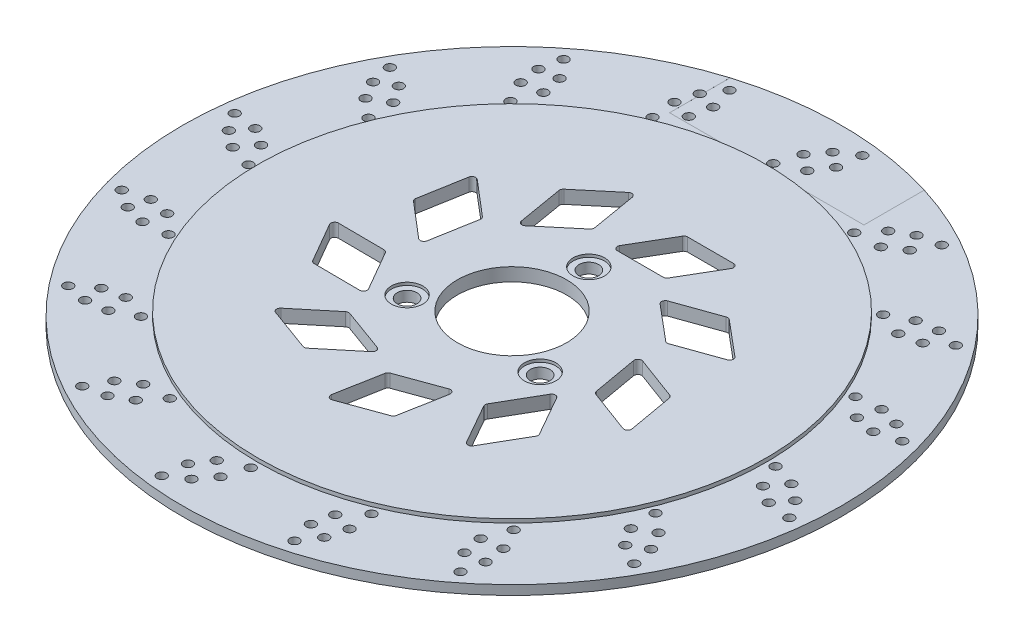
SolidWorks part; units mm, degrees
ref_plane "Płaszczyzna przednia" through (0, 0, 0) normal (0, 0, 1) x (1, 0, 0)
ref_plane "Płaszczyzna górna" through (0, 0, 0) normal (0, 1, 0) x (1, 0, 0)
ref_plane "Płaszczyzna prawa" through (0, 0, 0) normal (1, 0, 0) x (0, 0, -1)
sketch "Sketch1" plane through (0, 0, 0) normal (0, 1, 0) x (1, 0, 0)
  circle A0 centre (0, 0) radius 29
  circle A1 centre (0, 0) radius 175
  circle A2 centre (0, 0) radius 135
  dimension "D1" = 58
  dimension "D2" = 350
  dimension "D3" = 270
extrude "Boss-Extrude1" add sketch "Sketch1" along normal blind 7 contours A2 A0 region at (-131.1816, 0, 0)
extrude "Boss-Extrude2" add sketch "Sketch1<3>" along normal blind 5 contours A1 A2 region at (-170.0503, 0, 0)
sketch "Sketch1<3>" plane through (0, 0, 0) normal (0, 1, 0) x (1, 0, 0) same geometry as "Sketch1"
ref_plane "mocowanie tarczy" through (0, 7, 0) normal (0, 1, 0) x (1, 0, 0)
sketch "Sketch7" plane through (0, 7, 0) normal (0, 1, 0) x (1, 0, 0)
  circle A0 centre (0, 0) radius 40.8 construction
  circle A2 centre (0, 40.8) radius 5.2
  dimension "D1" = 81.6
  dimension "D3" = 10.4
extrude "Cut-Extrude9" cut sketch "Sketch7" against normal through all contours A2 region at (0, 7, -40.8)
sketch "Sketch11" plane through (0, 7, 0) normal (0, 1, 0) x (1, 0, 0)
  circle A0 centre (0, 40.8) radius 8.35
  dimension "D1" = 16.7
extrude "Cut-Extrude10" cut sketch "Sketch11" against normal blind 1.5 contours A0 region at (0, 7, -40.8)
pattern_circular "CirPattern1" count 3 over 360 about axis through (0, 7, 0) along (0, 1, 0) of "Cut-Extrude9"
pattern_circular "CirPattern2" count 3 over 360 about axis through (0, 7, 0) along (0, 1, 0) of "Cut-Extrude10"
ref_plane "dziury przy mocowaniu" through (0, 7, 0) normal (0, 1, 0) x (1, 0, 0)
sketch "Sketch13" plane through (0, 7, 0) normal (0, 1, 0) x (1, 0, 0)
  line L0 (0.1257, 55.8) -> (24.4722, 55.8)
  line L1 (26.1973, 56.788) -> (38.5161, 77.788)
  line L2 (36.791, 80.8) -> (12.4445, 80.8)
  line L3 (10.7194, 79.812) -> (-1.5993, 58.812)
  line L4 (80.1197, 38.2479) -> (61.4692, 53.8976)
  line L5 (59.5126, 54.2495) -> (36.5774, 46.0809)
  line L6 (56.57, 26.6632) -> (79.5052, 34.8318)
  line L7 (35.9629, 42.6648) -> (54.6133, 27.0152)
  line L8 (85.9596, -22.2) -> (81.7318, 1.7766)
  line L9 (80.4592, 3.3039) -> (57.6392, 11.7889)
  line L10 (60.4728, -15.9369) -> (83.2929, -24.4219)
  line L11 (54.9725, 9.567) -> (59.2002, -14.4096)
  line L12 (51.5779, -72.2596) -> (63.7512, -51.1749)
  line L13 (63.7581, -49.1869) -> (51.7309, -28.0186)
  line L14 (36.0798, -51.0793) -> (48.107, -72.2476)
  line L15 (48.2599, -28.0066) -> (36.0867, -49.0913)
  line L16 (-6.9376, -88.5074) -> (15.9406, -80.1804)
  line L17 (17.2237, -78.6619) -> (21.6171, -54.7151)
  line L18 (-5.1954, -62.3203) -> (-9.5888, -86.2671)
  line L19 (18.9659, -52.4748) -> (-3.9123, -60.8018)
  line L20 (-62.207, -63.3409) -> (-39.3288, -71.6678)
  line L21 (-37.3698, -71.3294) -> (-18.6115, -55.8091)
  line L22 (-44.0397, -44.4002) -> (-62.7979, -59.9205)
  line L23 (-19.2025, -52.3888) -> (-42.0807, -44.0618)
  line L24 (-88.3691, -8.5357) -> (-76.1958, -29.6204)
  line L25 (-74.4776, -30.6203) -> (-50.1317, -30.7887)
  line L26 (-62.2773, -5.7041) -> (-86.6232, -5.5357)
  line L27 (-48.3858, -27.7887) -> (-60.5591, -6.704)
  line L28 (-73.1823, 50.2641) -> (-77.41, 26.2875)
  line L29 (-76.7365, 24.4171) -> (-58.1947, 8.6389)
  line L30 (-51.3747, 35.6618) -> (-69.9165, 51.44)
  line L31 (-54.9289, 9.8148) -> (-50.7012, 33.7914)
  line L32 (-23.7527, 85.5456) -> (-42.4032, 69.8959)
  line L33 (-43.0896, 68.0302) -> (-39.0278, 44.0249)
  line L34 (-16.4333, 60.3419) -> (-20.4952, 84.3471)
  line L35 (-35.7702, 42.8265) -> (-17.1197, 58.4761)
  circle A0 centre (0, 40.8) radius 8.35 construction
  arc A1 (38.5161, 77.788) -> (36.791, 80.8) centre (36.791, 78.8) ccw
  arc A2 (24.4722, 55.8) -> (26.1973, 56.788) centre (24.4722, 57.8) ccw
  arc A3 (0.1257, 55.8) -> (-1.5993, 58.812) centre (0.1257, 57.8) cw
  arc A4 (10.7194, 79.812) -> (12.4445, 80.8) centre (12.4445, 78.8) cw
  arc A5 (35.9629, 42.6648) -> (36.5774, 46.0809) centre (37.2484, 44.1969) cw
  arc A6 (59.5126, 54.2495) -> (61.4692, 53.8976) centre (60.1837, 52.3655) cw
  arc A7 (79.5052, 34.8318) -> (80.1197, 38.2479) centre (78.8342, 36.7159) ccw
  arc A8 (54.6133, 27.0152) -> (56.57, 26.6632) centre (55.8989, 28.5473) ccw
  arc A9 (54.9725, 9.567) -> (57.6392, 11.7889) centre (56.9421, 9.9143) cw
  arc A10 (80.4592, 3.3039) -> (81.7318, 1.7766) centre (79.7622, 1.4293) cw
  arc A11 (83.2929, -24.4219) -> (85.9596, -22.2) centre (83.9899, -22.5473) ccw
  arc A12 (59.2002, -14.4096) -> (60.4728, -15.9369) centre (61.1699, -14.0623) ccw
  arc A13 (48.2599, -28.0066) -> (51.7309, -28.0186) centre (49.992, -29.0066) cw
  arc A14 (63.7581, -49.1869) -> (63.7512, -51.1749) centre (62.0191, -50.1749) cw
  arc A15 (48.107, -72.2476) -> (51.5779, -72.2596) centre (49.8459, -71.2596) ccw
  arc A16 (36.0867, -49.0913) -> (36.0798, -51.0793) centre (37.8187, -50.0913) ccw
  arc A17 (18.9659, -52.4748) -> (21.6171, -54.7151) centre (19.65, -54.3542) cw
  arc A18 (17.2237, -78.6619) -> (15.9406, -80.1804) centre (15.2566, -78.301) cw
  arc A19 (-9.5888, -86.2671) -> (-6.9376, -88.5074) centre (-7.6216, -86.628) ccw
  arc A20 (-3.9123, -60.8018) -> (-5.1954, -62.3203) centre (-3.2282, -62.6812) ccw
  arc A21 (-19.2025, -52.3888) -> (-18.6115, -55.8091) centre (-19.8865, -54.2682) cw
  arc A22 (-37.3698, -71.3294) -> (-39.3288, -71.6678) centre (-38.6447, -69.7885) cw
  arc A23 (-62.7979, -59.9205) -> (-62.207, -63.3409) centre (-61.5229, -61.4615) ccw
  arc A24 (-42.0807, -44.0618) -> (-44.0397, -44.4002) centre (-42.7647, -45.9412) ccw
  arc A25 (-48.3858, -27.7887) -> (-50.1317, -30.7887) centre (-50.1179, -28.7887) cw
  arc A26 (-74.4776, -30.6203) -> (-76.1958, -29.6204) centre (-74.4638, -28.6204) cw
  arc A27 (-86.6232, -5.5357) -> (-88.3691, -8.5357) centre (-86.637, -7.5357) ccw
  arc A28 (-60.5591, -6.704) -> (-62.2773, -5.7041) centre (-62.2911, -7.704) ccw
  arc A29 (-54.9289, 9.8148) -> (-58.1947, 8.6389) centre (-56.8986, 10.162) cw
  arc A30 (-76.7365, 24.4171) -> (-77.41, 26.2875) centre (-75.4404, 25.9402) cw
  arc A31 (-69.9165, 51.44) -> (-73.1823, 50.2641) centre (-71.2127, 49.9168) ccw
  arc A32 (-50.7012, 33.7914) -> (-51.3747, 35.6618) centre (-52.6708, 34.1387) ccw
  arc A33 (-35.7702, 42.8265) -> (-39.0278, 44.0249) centre (-37.0558, 44.3586) cw
  arc A34 (-43.0896, 68.0302) -> (-42.4032, 69.8959) centre (-41.1176, 68.3639) cw
  arc A35 (-20.4952, 84.3471) -> (-23.7527, 85.5456) centre (-22.4672, 84.0135) ccw
  arc A36 (-17.1197, 58.4761) -> (-16.4333, 60.3419) centre (-18.4053, 60.0082) ccw
  point P12 (-3.3662, 55.8)
  point P15 (11.299, 80.8)
  point P115 (-0.0001, 0.0016)
  dimension "D3" = 2
  dimension "D1" = 25
  dimension "D2" = 15
  dimension "D4" = 9
extrude "Cut-Extrude11" cut sketch "Sketch13" against normal through all
ref_plane "nawierty" through (0, 5, 0) normal (0, 1, 0) x (1, 0, 0)
sketch "Sketch14" plane through (0, 5, 0) normal (0, 1, 0) x (1, 0, 0)
  arc A0 (-0.6141, 139.3555) -> (19.3718, 166.6528) centre (33.6045, 135.2673) cw construction
  circle A1 centre (19.3718, 166.6528) radius 2.5
  circle A3 centre (-0.6141, 139.3555) radius 2.5
  circle A4 centre (9.924, 160.3044) radius 2.5
  circle A5 centre (3.2411, 151.5671) radius 2.5
  arc A6 (19.3718, 166.6528) -> (-0.6141, 139.3555) centre (-4.6233, 163.2559) cw construction
  circle A7 centre (17.8673, 154.2295) radius 2.5
  circle A8 centre (11.7642, 145.048) radius 2.5
  dimension "D1" = 5
  dimension "D3" = 10
extrude "Cut-Extrude12" cut sketch "Sketch14" against normal through all
pattern_circular "CirPattern3" count 16 over 360 about axis through (0, 5, 0) along (0, 1, 0) of "Cut-Extrude12"
sketch "Sketch15" plane through (0, 0, 0) normal (0, 1, 0) x (1, 0, 0)
  circle A0 centre (0, 0) radius 175
  circle A1 centre (0, 0) radius 135
  dimension "D1" = 270
extrude "Cut-Extrude13" cut sketch "Sketch15" along normal blind 0.01
sketch "Sketch16" plane through (0, 5, 0) normal (0, 1, 0) x (1, 0, 0)
  line L1 (-51.4501, 175.6507) -> (51.7659, 175.6507)
  line L2 (-51.4501, 175.6507) -> (-51.4501, 135.1174)
  line L3 (-51.4501, 135.1174) -> (51.7659, 135.1174)
  line L4 (51.7659, 175.6507) -> (51.7659, 135.1174)
extrude "Cut-Extrude14" cut sketch "Sketch16" against normal blind 0.01
ref_plane "Plane1" through (0, 0.01, 0) normal (0, -1, 0) x (-1, 0, 0)
sketch "Sketch17" plane through (0, 0.01, 0) normal (0, -1, 0) x (-1, 0, 0)
  line L1 (-52.3224, 177.6466) -> (49.8176, 177.6466)
  line L2 (-52.3224, 177.6466) -> (-52.3224, 135.2656)
  line L3 (-52.3224, 135.2656) -> (49.8176, 135.2656)
  line L4 (49.8176, 177.6466) -> (49.8176, 135.2656)
extrude "Cut-Extrude15" cut sketch "Sketch17" against normal blind 0.01
